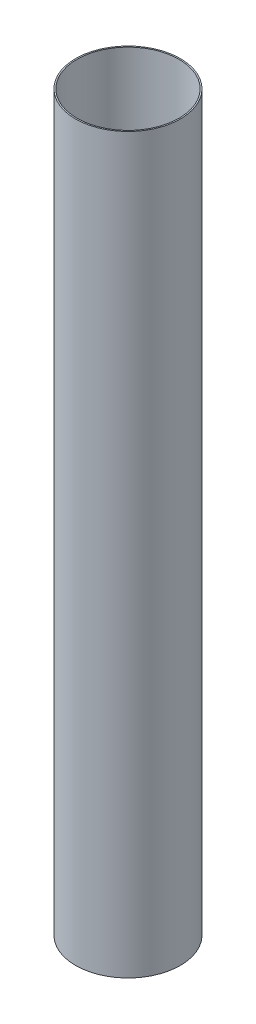
SolidWorks part; units mm, degrees
material "6061-T6 (SS)"
ref_plane "Front Plane" through (0, 0, 0) normal (0, 0, 1) x (1, 0, 0)
ref_plane "Top Plane" through (0, 0, 0) normal (0, 1, 0) x (1, 0, 0)
ref_plane "Right Plane" through (0, 0, 0) normal (1, 0, 0) x (0, 0, -1)
sketch "Sketch5" plane through (0, 0, 0) normal (0, 1, 0) x (1, 0, 0)
  circle A0 centre (0, 0) radius 50.8
  circle A1 centre (0, 0) radius 49.53
  dimension "D1" = 101.6
  dimension "D2" = 99.06
extrude "Boss-Extrude1" add sketch "Sketch5" against normal blind 711.2
